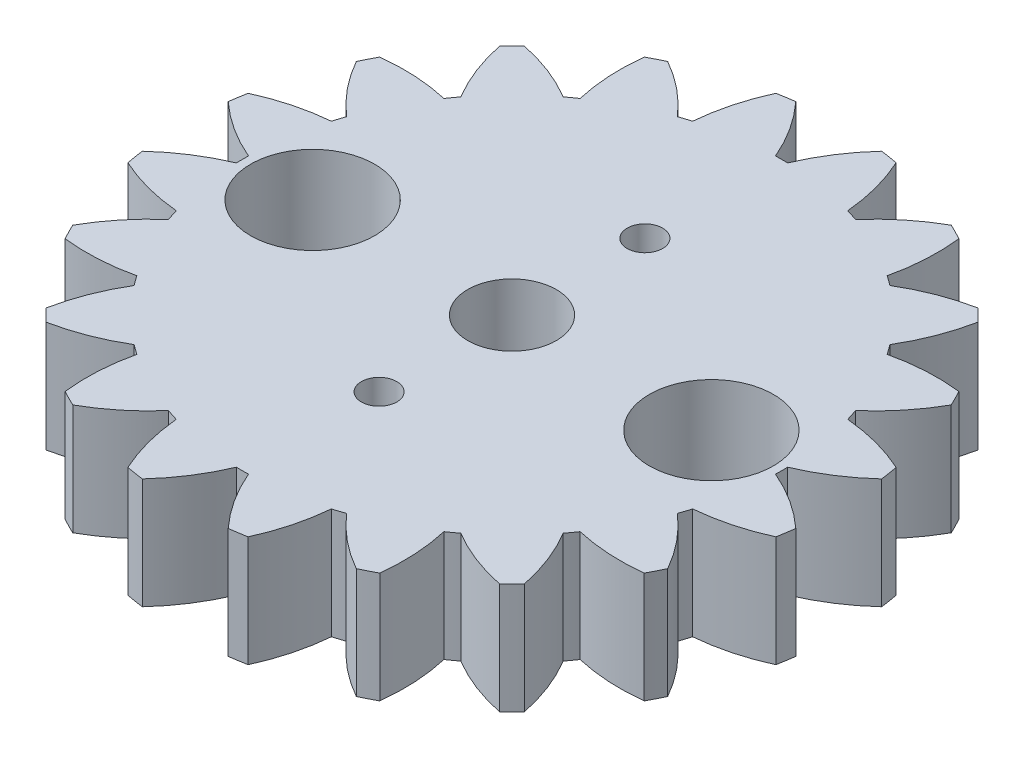
SolidWorks part; units mm, degrees
ref_plane "Front" through (0, 0, 0) normal (0, 0, 1) x (1, 0, 0)
ref_plane "Top" through (0, 0, 0) normal (0, 1, 0) x (1, 0, 0)
ref_plane "Right" through (0, 0, 0) normal (1, 0, 0) x (0, 0, -1)
sketch "Sketch1" plane through (0, 0, 0) normal (0, 1, 0) x (1, 0, 0)
  line L0 (0, 0) -> (0, 14.875) construction
  circle A0 centre (0, 0) radius 14.875
  dimension "D1" = 29.75
extrude "Boss-Extrude1" add sketch "Sketch1" along normal blind 5
sketch "Sketch2" plane through (0, 5, 0) normal (0, 1, 0) x (1, 0, 0)
  line L0 (0, 14.875) -> (0, 0) construction
  line L1 (0, 0) -> (-0.9681, 13.488) construction
  line L2 (-2.1243, 14.7225) -> (0, 0) construction
  circle A0 centre (0, 0) radius 12.1705 construction
  circle A1 centre (0, 0) radius 13.5227 construction
  circle A3 centre (0, 0) radius 14.875 construction
  arc A4 (-0.2735, 12.1674) -> (-1.9374, 14.7483) centre (-8.5588, 8.6526) ccw
  arc A5 (0.2735, 12.1674) -> (-0.2735, 12.1674) centre (0, 0) ccw
  arc A6 (1.9374, 14.7483) -> (-1.9374, 14.7483) centre (0, 0) ccw
  arc A8 (0.2735, 12.1674) -> (1.9374, 14.7483) centre (8.5588, 8.6526) cw
  arc A9 (-3.1773, 11.7484) -> (-2.3109, 14.6944) centre (5.7636, 10.7192) cw construction
  dimension "D1" = 29.75
  dimension "D2" = 27.0455
  dimension "D3" = 24.3409
  dimension "D4" = 4.2483
  dimension "D5" = 9
extrude "Cut-Extrude1" cut sketch "Sketch2" against normal up to surface (5 mm away) up to face at (0, 0, 14.875)
pattern_circular "CirPattern1" count 20 over 360 about axis through (0, 5, 0) along (0, -1, 0) of "Cut-Extrude1" reverse direction yes
sketch "Sketch3" plane through (0, 5, 0) normal (0, 1, 0) x (1, 0, 0)
  circle A0 centre (0, 0) radius 2
  dimension "D1" = 4
extrude "Cut-Extrude2" cut sketch "Sketch3" against normal up to surface (5 mm away) up to face at (0, 0, 0)
sketch "Sketch4" plane through (0, 5, 0) normal (0, 1, 0) x (1, 0, 0)
  line L0 (0, 0) -> (0, 6) construction
  line L1 (0, 0) -> (0, -6) construction
  line L2 (0, 0) -> (-9, 0) construction
  line L3 (0, 0) -> (9, 0) construction
  circle A0 centre (0, 6) radius 0.8
  circle A1 centre (0, -6) radius 0.8
  circle A4 centre (-9, 0) radius 2.8
  circle A5 centre (9, 0) radius 2.8
  dimension "D2" = 1.6
  dimension "D4" = 5.6
  dimension "D1" = 6
  dimension "D3" = 9
extrude "Cut-Extrude3" cut sketch "Sketch4" against normal blind 5
equation "\"od\"= 29.75'outside diameter"
equation "\"n\" = 20'number of teeth"
equation "\"m\"= \"od\" / ( \"n\" + 2 )'module"
equation "\"p\"= \"m\" * pi'pitch"
equation "\"d\"= \"m\" * \"n\"'primitive diameter"
equation "\"da\"= \"d\" + 2 * \"m\"'head diamater"
equation "\"df\"= \"d\" - 2 * \"m\"'foot diameter"
equation "\"D1@Sketch1\"=\"da\""
equation "\"D1@Sketch2\"=\"da\""
equation "\"D2@Sketch2\"=\"d\""
equation "\"D4@Sketch2\"=\"p\""
equation "\"D1@CirPattern1\"=\"n\""
